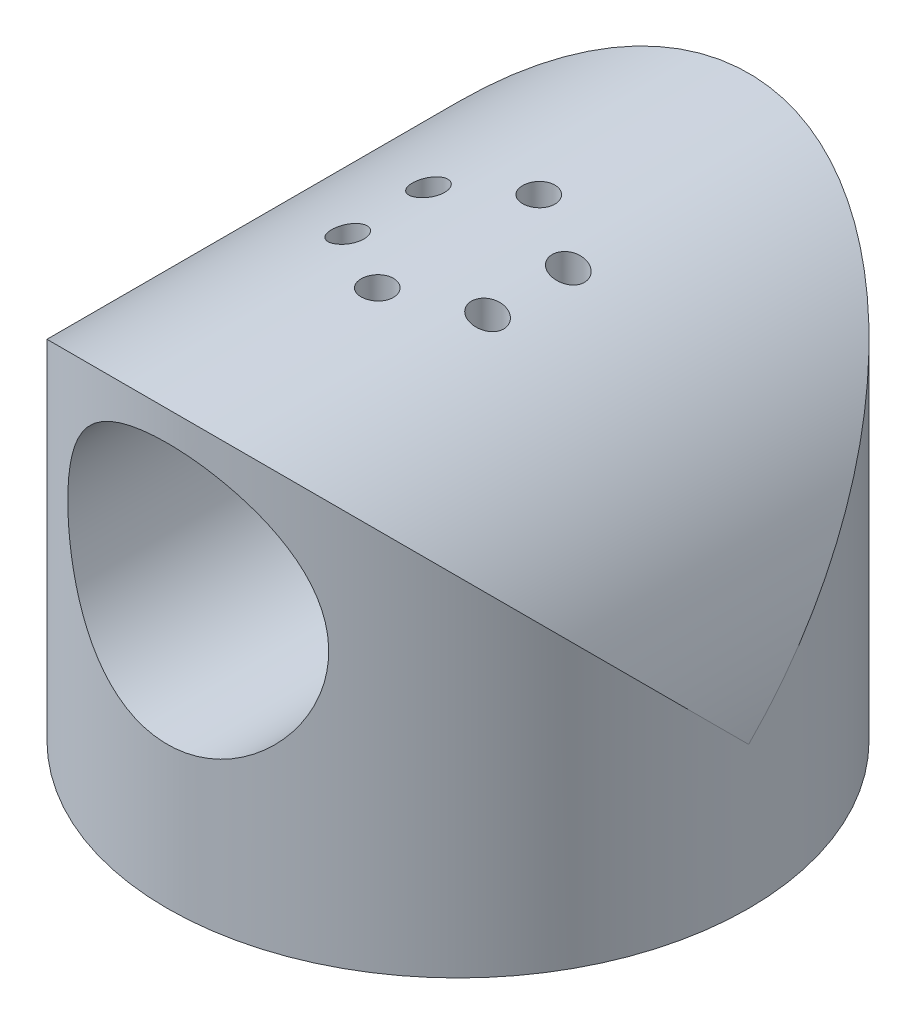
SolidWorks part; units mm, degrees
ref_plane "前视基准面" through (0, 0, 0) normal (0, 0, 1) x (1, 0, 0)
ref_plane "上视基准面" through (0, 0, 0) normal (0, 1, 0) x (1, 0, 0)
ref_plane "右视基准面" through (0, 0, 0) normal (1, 0, 0) x (0, 0, -1)
other "Configuration Table"
sketch "草图1" plane through (0, 0, 0) normal (0, 1, 0) x (1, 0, 0)
  circle A3 centre (0, 0) radius 40
  circle A4 centre (0, 0) radius 45
  dimension "D1" = 90
  dimension "D2" = 80
extrude "凸台-拉伸1" add sketch "草图1" along normal blind 17
sketch "草图4" plane through (0, 0, 0) normal (0, 0, 1) x (1, 0, 0)
  line L0 (0, -1000) -> (0, 49000) construction
  line L4 (-45, 22) -> (-45, 17)
  line L5 (-45, 17) -> (45, 17)
  line L6 (45, 17) -> (45, 22)
  line L7 (-45, 22) -> (45, 22) construction
  circle A0 centre (0, 42.2) radius 20.2
  arc A1 (-45, 22) -> (45, 22) centre (0, 22) cw
  dimension "D1" = 40.4
  dimension "D2" = 5
extrude "凸台-拉伸3" add sketch "草图4" along normal blind 45 and the other way blind 45
sketch "草图5" plane through (0, 17, 0) normal (0, -1, 0) x (1, 0, 0)
  line L1 (-45, -45) -> (45, -45)
  line L2 (-45, -45) -> (-45, 45)
  line L3 (-45, 45) -> (45, 45)
  line L4 (45, -45) -> (45, 45)
  line L5 (-45, -45) -> (45, 45) construction
  line L6 (-45, 45) -> (45, -45) construction
  circle A0 centre (0, 0) radius 45
  circle A1 centre (0, 0) radius 45 construction
  line M1 (-45, 45) -> (-45, 0)
  arc M2 (-45, 0) -> (0, 45) centre (0, 0) cw
  line M3 (0, 45) -> (-45, 45)
extrude "切除-拉伸1" cut sketch "草图5" against normal through all contours M3 M1 M2 | A0 L4 L3 | A0 L1 L4 | A0 L2 L1 region at (-34.9484, 17, -34.9484) region at (34.9484, 17, -34.9484) region at (-34.9484, 17, 34.9484) region at (34.9484, 17, 34.9484)
sketch "草图6" plane through (0, 17, 0) normal (0, -1, 0) x (1, 0, 0)
  line L0 (-1000, 0) -> (49000, 0) construction
  line L1 (-5.1, 8.8335) -> (0, 0) construction
  circle A0 centre (0, 0) radius 10.2 construction
  circle A2 centre (-5.1, 8.8335) radius 1.5
  circle A3 centre (10.2, 0) radius 1.5
  circle A4 centre (-5.1, -8.8335) radius 1.5
  point P3 (10.2, 0)
  dimension "D1" = 20.4
  dimension "D3" = 3
  dimension "D4" = 3
  dimension "D2" = 60
extrude "切除-拉伸3" cut sketch "草图6" against normal blind 4.8
ref_plane "基准面1" through (0, 20, 0) normal (0, -1, 0) x (-1, 0, 0)
sketch "草图8" plane through (0, 17, 0) normal (0, -1, 0) x (1, 0, 0)
  line L0 (-1000, 0) -> (49000, 0) construction
  line L1 (0, -1000) -> (0, 49000) construction
  line L2 (10.8253, 6.25) -> (0, 0) construction
  circle A0 centre (0, 0) radius 12.5 construction
  circle A1 centre (0, 12.5) radius 1.5
  circle A2 centre (10.8253, 6.25) radius 1.5
  circle A3 centre (-10.8253, 6.25) radius 1.5
  circle A4 centre (-10.8253, -6.25) radius 1.5
  circle A5 centre (10.8253, -6.25) radius 1.5
  circle A6 centre (0, -12.5) radius 1.5
  dimension "D2" = 25
  dimension "D3" = 3
  dimension "D4" = 3
  dimension "D1" = 30
extrude "切除-拉伸4" cut sketch "草图8" against normal through all
sketch "草图9" plane through (0, 20, 0) normal (0, -1, 0) x (-1, 0, 0)
  line L0 (-1000, 0) -> (49000, 0) construction
  line L1 (0, -1000) -> (0, 49000) construction
  circle A0 centre (0, 12.5) radius 2.5
  circle A1 centre (10.8253, 6.25) radius 2.5
  circle A2 centre (-10.8253, 6.25) radius 2.5
  circle A3 centre (-10.8253, -6.25) radius 2.5
  circle A4 centre (10.8253, -6.25) radius 2.5
  circle A5 centre (0, -12.5) radius 2.5
  dimension "D1" = 5
  dimension "D2" = 5
extrude "切除-拉伸5" cut sketch "草图9" against normal through all
